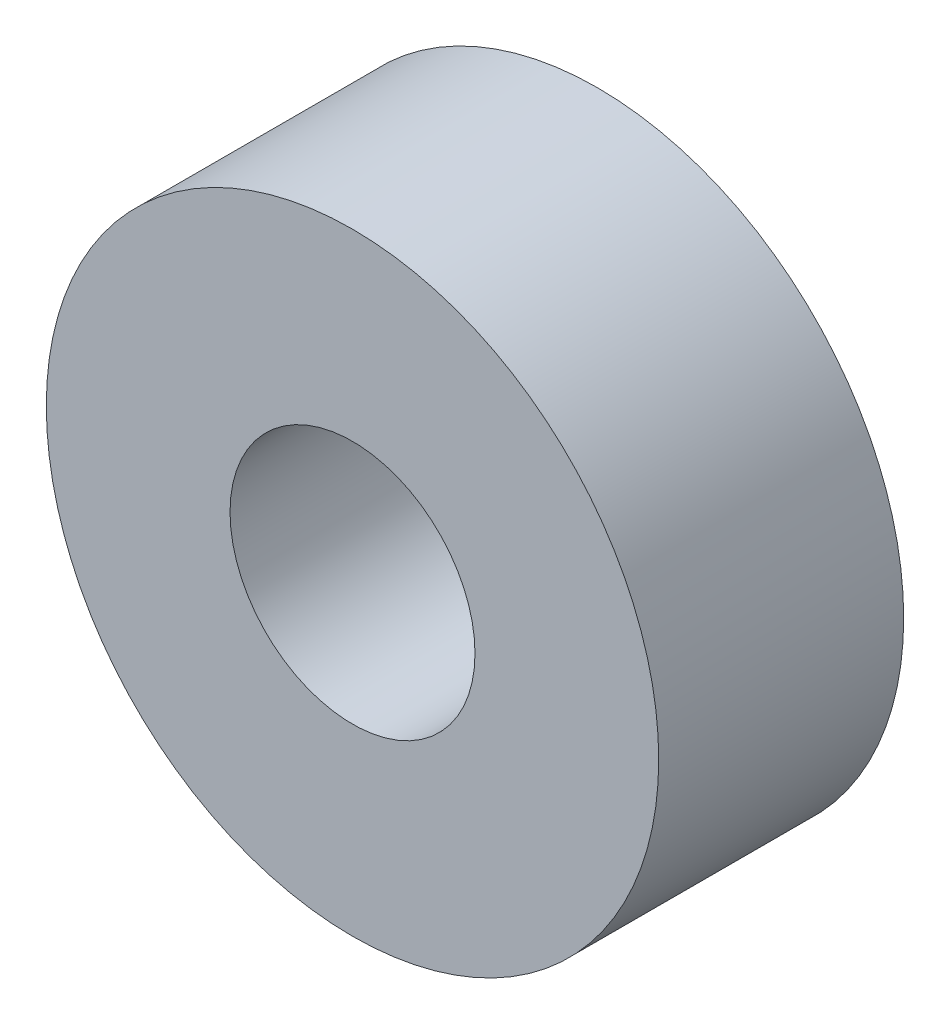
SolidWorks part; units mm, degrees
material "AISI 303 Stainless"
ref_plane "Front Plane" through (0, 0, 0) normal (0, 0, 1) x (1, 0, 0)
ref_plane "Top Plane" through (0, 0, 0) normal (0, 1, 0) x (1, 0, 0)
ref_plane "Right Plane" through (0, 0, 0) normal (1, 0, 0) x (0, 0, -1)
other "Configuration Table"
sketch "Sketch1" plane through (0, 0, 0) normal (0, 0, 1) x (1, 0, 0)
  circle A0 centre (0, 0) radius 3.175
  circle A1 centre (0, 0) radius 7.9375
  dimension "D1" = 6.35
  dimension "D2" = 15.875
extrude "Boss-Extrude1" add sketch "Sketch1" along normal blind 6.35
